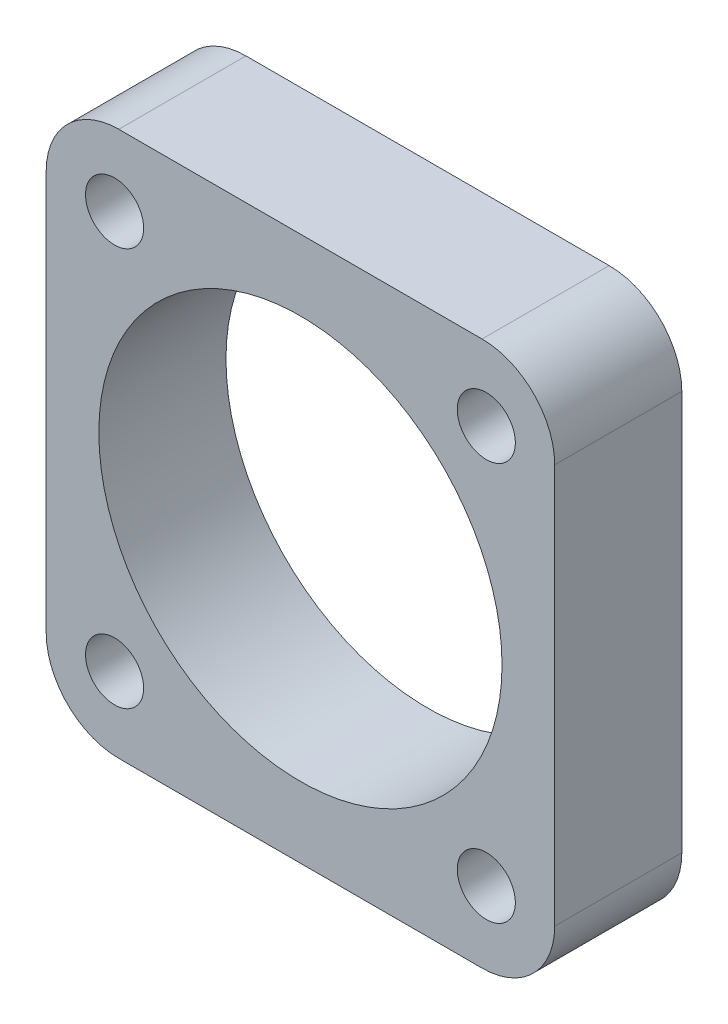
SolidWorks part; units mm, degrees
ref_plane "Front Plane" through (0, 0, 0) normal (0, 0, 1) x (1, 0, 0)
ref_plane "Top Plane" through (0, 0, 0) normal (0, 1, 0) x (1, 0, 0)
ref_plane "Right Plane" through (0, 0, 0) normal (1, 0, 0) x (0, 0, -1)
sketch "Sketch1" plane through (0, 0, 0) normal (0, 0, 1) x (1, 0, 0)
  line L0 (0, 15) -> (0, -15) construction
  line L1 (-14, 15) -> (14, 15)
  line L2 (-14, 15) -> (-14, -15)
  line L3 (-14, -15) -> (14, -15)
  line L4 (14, 15) -> (14, -15)
  line L5 (-14, 15) -> (14, -15) construction
  line L6 (-14, -15) -> (14, 15) construction
  line L7 (-10.2348, 7.6172) -> (-7.3348, 9.2915)
  line L8 (-7.3348, 9.2915) -> (-7.3348, 12.6401)
  line L9 (-7.3348, 12.6401) -> (-10.2348, 14.3145)
  line L10 (-10.2348, 14.3145) -> (-13.1348, 12.6401)
  line L11 (-13.1348, 12.6401) -> (-13.1348, 9.2915)
  line L12 (-13.1348, 9.2915) -> (-10.2348, 7.6172)
  line L19 (13.1348, 9.2915) -> (10.2348, 7.6172)
  line L20 (13.1348, 12.6401) -> (13.1348, 9.2915)
  line L21 (10.2348, 14.3145) -> (13.1348, 12.6401)
  line L22 (7.3348, 12.6401) -> (10.2348, 14.3145)
  line L23 (7.3348, 9.2915) -> (7.3348, 12.6401)
  line L24 (10.2348, 7.6172) -> (7.3348, 9.2915)
  line L25 (14, 0) -> (-14, 0) construction
  line L26 (-10.2348, -7.6172) -> (-7.3348, -9.2915)
  line L27 (-7.3348, -9.2915) -> (-7.3348, -12.6401)
  line L28 (-7.3348, -12.6401) -> (-10.2348, -14.3145)
  line L29 (-10.2348, -14.3145) -> (-13.1348, -12.6401)
  line L30 (-13.1348, -12.6401) -> (-13.1348, -9.2915)
  line L31 (-13.1348, -9.2915) -> (-10.2348, -7.6172)
  line L32 (13.1348, -9.2915) -> (10.2348, -7.6172)
  line L33 (13.1348, -12.6401) -> (13.1348, -9.2915)
  line L34 (10.2348, -14.3145) -> (13.1348, -12.6401)
  line L35 (7.3348, -12.6401) -> (10.2348, -14.3145)
  line L36 (7.3348, -9.2915) -> (7.3348, -12.6401)
  line L37 (10.2348, -7.6172) -> (7.3348, -9.2915)
  circle A0 centre (0, 0) radius 11.1
  circle A1 centre (-10.2348, 10.9658) radius 1.6
  circle A2 centre (-10.2348, 10.9658) radius 2.9 construction
  circle A4 centre (10.2348, 10.9658) radius 1.6
  circle A5 centre (-10.2348, -10.9658) radius 1.6
  circle A6 centre (10.2348, -10.9658) radius 1.6
  dimension "D1" = 22.2
  dimension "D4" = 3.2
  dimension "D2" = 28
  dimension "D3" = 30
  dimension "D5" = 5.8
  dimension "D6" = 15
extrude "Boss-Extrude1" add sketch "Sketch1" along normal blind 7 contours L4 L1 L2 L3 A0 L37 L32 L33 L34 L35 L36 L12 L11 L10 L9 L8 L7 L19 L24 L23 L22 L21 L20 L30 L31 L26 L27 L28 L29 | L24 L19 L20 L21 L22 L23 A4 | L11 L12 L7 L8 L9 L10 A1 | L31 L30 L29 L28 L27 L26 A5 | L32 L37 L36 L35 L34 L33 A6 region at (0, 14.5896, 0) region at (-11.6405, 8.5311, 0) region at (11.6405, 8.5311, 0) region at (-8.8291, -8.5311, 0) region at (13.0462, -10.9658, 0)
fillet "Fillet1" [suppressed] radius 10
extrude "Cut-Extrude3" cut sketch "Sketch1<4>" along normal blind 3 contours L24 L19 L20 L21 L22 L23 A4 | L11 L12 L7 L8 L9 L10 A1 | L31 L30 L29 L28 L27 L26 A5 | L32 L37 L36 L35 L34 L33 A6 region at (-11.6405, 8.5311, 0) region at (11.6405, 8.5311, 0) region at (-8.8291, -8.5311, 0) region at (13.0462, -10.9658, 0)
sketch "Sketch1<4>" plane through (0, 0, 0) normal (0, 0, 1) x (1, 0, 0) same geometry as "Sketch1"
fillet "Fillet5" radius 4 4 edges at (-14, 15, 3.5) (-14, -15, 3.5) (14, 15, 3.5) (14, -15, 3.5)
